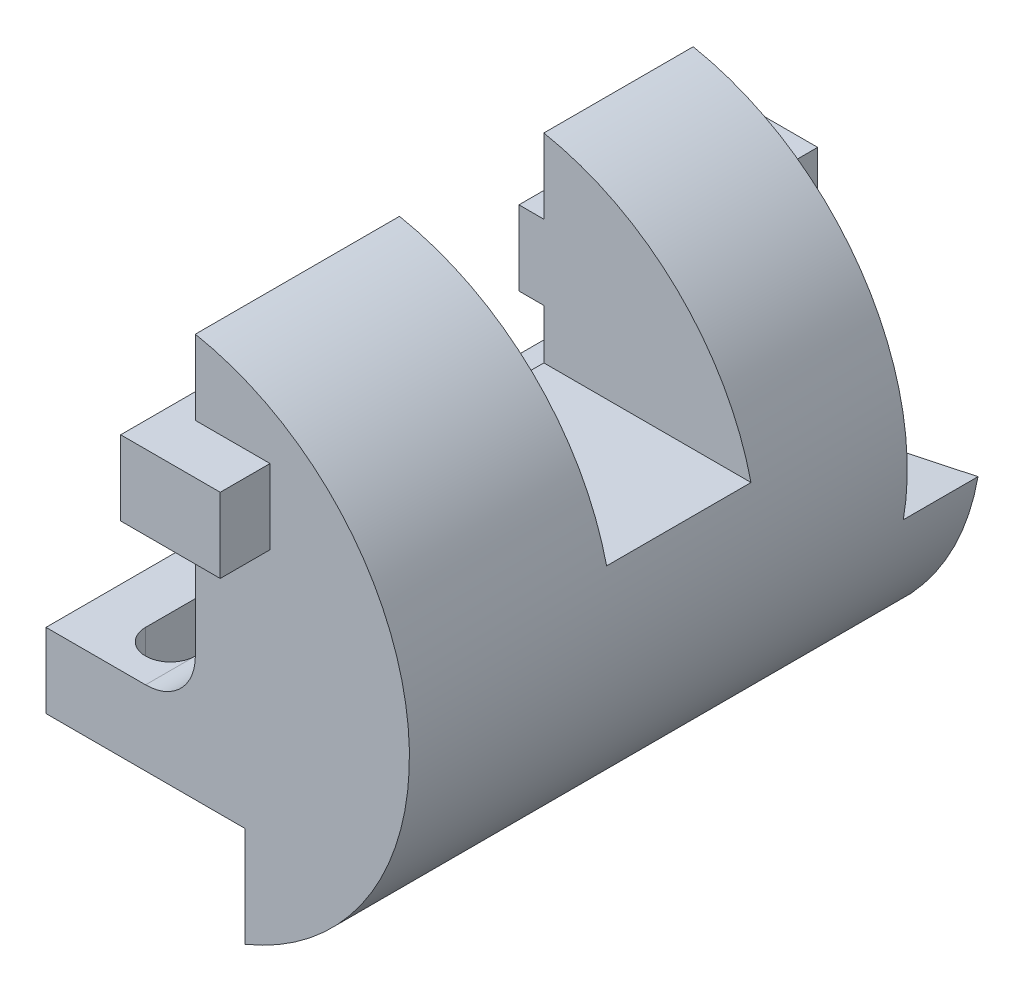
SolidWorks part; units mm, degrees
material "Silicon Dioxide"
ref_plane "Front Plane" through (0, 0, 0) normal (0, 0, 1) x (1, 0, 0)
ref_plane "Top Plane" through (0, 0, 0) normal (0, 1, 0) x (1, 0, 0)
ref_plane "Right Plane" through (0, 0, 0) normal (1, 0, 0) x (0, 0, -1)
sketch "Sketch1" plane through (0, 0, 0) normal (0, 0, 1) x (1, 0, 0)
  line L0 (10, -35.1296) -> (10, -15)
  line L1 (10, -15) -> (-30, -15)
  line L2 (-30, -15) -> (-30, 0)
  line L3 (-30, 0) -> (0, 0)
  line L4 (0, 0) -> (0, 66)
  arc A1 (10, -35.1296) -> (0, 66) centre (-10, 13.9519) ccw
  dimension "D3" = 10
  dimension "D5" = 53
  dimension "D1" = 40
  dimension "D2" = 15
  dimension "D4" = 20
  dimension "D6" = 66
extrude "Boss-Extrude1" add sketch "Sketch1" along normal blind 100 contours L4 A1 L0 L1 L2 L3
sketch "Sketch2" plane through (0, 0, 0) normal (0, 0, -1) x (-1, 0, 0)
  line L0 (30, -10.5291) -> (30, -15)
  line L2 (30, -15) -> (30, -10.5291)
  line L3 (30, -10.5291) -> (-42.2072, 4.819)
  line L4 (-10, -15) -> (-10, -35.1296)
  line L5 (-10, -15) -> (30, -15)
  arc A0 (0, 66) -> (-10, -35.1296) centre (10, 13.9519) ccw construction
  arc M5 (0, 66) -> (-10, -35.1296) centre (10, 13.9519) ccw
  line M6 (-10, -35.1296) -> (-10, -15)
  line M7 (-10, -15) -> (30, -15)
  line M8 (30, -15) -> (30, 0)
  dimension "D1" = 4.4709
  dimension "D2" = 78
extrude "Boss-Extrude2" add sketch "Sketch2" along normal blind 15 contours L3 M8 M5 M6 M7 region at (13.646, -11.8762, 0)
sketch "Sketch4" plane through (0, 0, 0) normal (0, 1, 0) x (1, 0, 0)
  line L0 (-20, -10) -> (-20, -90)
  line L1 (-10, -90) -> (-10, -10)
  line L3 (-30, -100) -> (-30, 0) construction
  line L4 (-30, 0) -> (42.2072, 0) construction
  line L5 (-30, -100) -> (0, -100) construction
  arc A0 (-20, -90) -> (-10, -90) centre (-15, -90) ccw
  arc A1 (-10, -10) -> (-20, -10) centre (-15, -10) ccw
  point P5 (0, 0)
  dimension "D1" = 5
  dimension "D2" = 10
  dimension "D3" = 10
  dimension "D4" = 15
extrude "Cut-Extrude1" cut sketch "Sketch4" against normal up to next and the other way through all
sketch "Sketch5" plane through (0, 0, 100) normal (0, 0, 1) x (1, 0, 0)
  line L1 (-5, 51) -> (15, 51)
  line L2 (-5, 51) -> (-5, 36)
  line L3 (-5, 36) -> (15, 36)
  line L4 (15, 51) -> (15, 36)
  point P4 (0, 0)
  dimension "D1" = 15
  dimension "D2" = 5
  dimension "D3" = 15
  dimension "D4" = 15
extrude "Boss-Extrude3" add sketch "Sketch5" against normal blind 110 and the other way blind 10
sketch "Sketch6" plane through (0, 0, 0) normal (-1, 0, 0) x (0, 0, 1)
  line L0 (100, 66) -> (0, 66) construction
  line L1 (30, 66) -> (59, 66)
  line L2 (30, 66) -> (30, 26)
  line L3 (30, 26) -> (59, 26)
  line L4 (59, 66) -> (59, 26)
  point P6 (0, 0)
  dimension "D1" = 40
  dimension "D2" = 30
  dimension "D3" = 29
extrude "Cut-Extrude2" cut sketch "Sketch6" against normal through all both and the other way through all
fillet "Fillet1" radius 10 1 edges at (0, 0, 50)
equation "\"a\"= 53mm'\""
equation "\"b\"= 66mm"
equation "\"c\"= 29mm"
